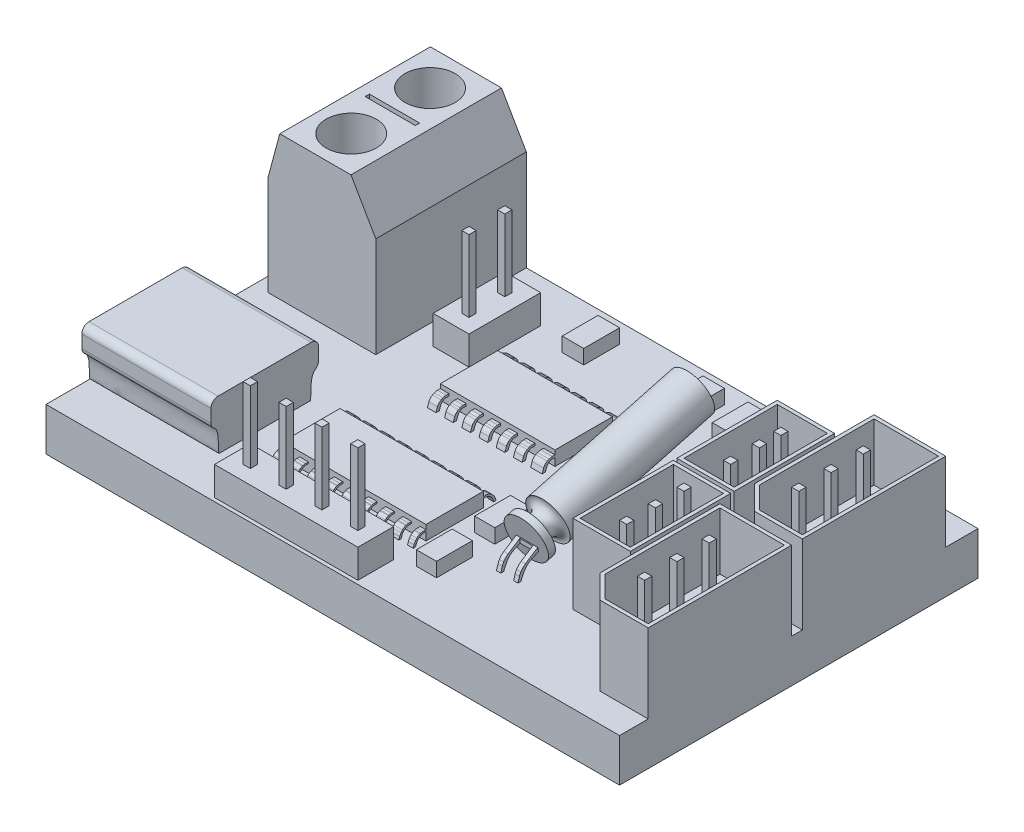
SolidWorks part; units mm, degrees
ref_plane "Front Plane" through (0, 0, 0) normal (0, 0, 1) x (1, 0, 0)
ref_plane "Top Plane" through (0, 0, 0) normal (0, 1, 0) x (1, 0, 0)
ref_plane "Right Plane" through (0, 0, 0) normal (1, 0, 0) x (0, 0, -1)
sketch "Sketch2" plane through (0, 0, 0) normal (0, 1, 0) x (1, 0, 0)
  line L1 (20, -12.5) -> (-20, -12.5)
  line L2 (20, -12.5) -> (20, 12.5)
  line L3 (20, 12.5) -> (-20, 12.5)
  line L4 (-20, -12.5) -> (-20, 12.5)
  line L5 (20, -12.5) -> (-20, 12.5) construction
  line L6 (20, 12.5) -> (-20, -12.5) construction
  point P0 (0, 0)
  dimension "D1" = 40
  dimension "D2" = 25
extrude "Boss-Extrude1" add sketch "Sketch2" against normal blind 3
sketch "Sketch3" plane through (0, 0, 0) normal (0, 1, 0) x (1, 0, 0)
  line L0 (20, 12.5) -> (-20, 12.5) construction
  line L1 (-19, 12.5) -> (-11.5, 12.5)
  line L2 (-19, 12.5) -> (-19, 2)
  line L3 (-19, 2) -> (-11.5, 2)
  line L4 (-11.5, 12.5) -> (-11.5, 2)
  line L5 (-20, 12.5) -> (-20, -12.5) construction
  dimension "D1" = 7.5
  dimension "D2" = 10.5
  dimension "D3" = 1
extrude "Boss-Extrude2" add sketch "Sketch3" along normal blind 10
sketch "Sketch4" plane through (0, 0, -2) normal (0, 0, 1) x (1, 0, 0)
  line L0 (-19, 7) -> (-18.1962, 10)
  line L1 (-19, 10) -> (-19, 0) construction
  line L2 (-19, 10) -> (-11.5, 10) construction
  line L3 (-18.1962, 10) -> (-19, 10)
  line L4 (-19, 10) -> (-19, 7)
  line L5 (-11.5, 7) -> (-13.2321, 10)
  line L6 (-11.5, 10) -> (-11.5, 0) construction
  line L7 (-13.2321, 10) -> (-11.5, 10)
  line L8 (-11.5, 10) -> (-11.5, 7)
  dimension "D1" = 3
  dimension "D2" = 3
  dimension "D3" = 15
  dimension "D4" = 30
extrude "Cut-Extrude1" cut sketch "Sketch4" against normal up to surface (10.5 mm away) up to face at (-7.625, 1.75, -12.5)
sketch "Sketch5" plane through (0, 10, 0) normal (0, 1, 0) x (1, 0, 0)
  line L0 (-13.2321, 12.5) -> (-18.1962, 12.5) construction
  line L1 (-17.4641, 7.522) -> (-13.9641, 7.522)
  line L2 (-17.4641, 7.522) -> (-17.4641, 7.222)
  line L3 (-17.4641, 7.222) -> (-13.9641, 7.222)
  line L4 (-13.9641, 7.522) -> (-13.9641, 7.222)
  line L5 (-19, 2) -> (-11.5, 2) construction
  circle A0 centre (-15.7141, 10) radius 1.75
  circle A1 centre (-15.7141, 4.5) radius 1.75
  point P10 (-15.7141, 12.5)
  point P11 (-15.7141, 7.522)
  dimension "D3" = 3.5
  dimension "D4" = 3.5
  dimension "D1" = 0.3
  dimension "D2" = 3.5
  dimension "D5" = 2.5
  dimension "D6" = 2.5
extrude "Cut-Extrude2" cut sketch "Sketch5" against normal blind 5
sketch "Sketch6" plane through (-19, 0, 0) normal (-1, 0, 0) x (0, 0, 1)
  line L0 (-2, 7) -> (-2, 0) construction
  line L1 (-12, 5.5) -> (-7.5, 5.5)
  line L2 (-12, 5.5) -> (-12, 1)
  line L3 (-12, 1) -> (-7.5, 1)
  line L4 (-7.5, 5.5) -> (-7.5, 1)
  line L5 (-12, 5.5) -> (-7.5, 1) construction
  line L6 (-12, 1) -> (-7.5, 5.5) construction
  line L7 (-7, 5.5) -> (-2.5, 5.5)
  line L8 (-7, 5.5) -> (-7, 1)
  line L9 (-7, 1) -> (-2.5, 1)
  line L10 (-2.5, 5.5) -> (-2.5, 1)
  line L11 (-7, 5.5) -> (-2.5, 1) construction
  line L12 (-7, 1) -> (-2.5, 5.5) construction
  line L13 (-12.5, 7) -> (-12.5, 0) construction
  line L14 (-12.5, 0) -> (-2, 0) construction
  point P0 (-9.75, 3.25)
  point P5 (-4.75, 3.25)
  dimension "D1" = 4.5
  dimension "D2" = 4.5
  dimension "D3" = 4.5
  dimension "D4" = 4.5
  dimension "D5" = 0.5
  dimension "D6" = 0.5
  dimension "D7" = 1
extrude "Cut-Extrude3" cut sketch "Sketch6" against normal blind 5
sketch "Sketch7" plane through (0, 0, 0) normal (0, 1, 0) x (1, 0, 0)
  line L0 (-20, 12.5) -> (-20, -12.5) construction
  line L1 (-11, -10) -> (-20, -10)
  line L2 (-11, -10) -> (-11, -2.5)
  line L3 (-11, -2.5) -> (-20, -2.5)
  line L4 (-20, -10) -> (-20, -2.5)
  line L5 (-11, -10) -> (-20, -2.5) construction
  line L6 (-11, -2.5) -> (-20, -10) construction
  line L7 (-20, -12.5) -> (20, -12.5) construction
  point P0 (-15.5, -6.25)
  dimension "D1" = 7.5
  dimension "D2" = 9
  dimension "D3" = 2.5
extrude "Boss-Extrude3" add sketch "Sketch7" along normal blind 3.5
sketch "Sketch8" plane through (-20, 0, 0) normal (-1, 0, 0) x (0, 0, 1)
  line L0 (6.25, 5.2143) -> (6.25, -0.441) construction
  line L1 (2.5, 3.5) -> (10, 3.5) construction
  line L2 (2.5, 3.5) -> (2.5, 0) construction
  line L3 (2.5, 0) -> (3.1127, 0)
  line L4 (2.5, 1.75) -> (2.5, 0)
  line L5 (10, 1.75) -> (10, 0)
  line L6 (10, 0) -> (9.3873, 0)
  spline S0 degree 3 poles (2.5, 1.75) (3.2855, 1.8357) (2.8866, -0.1418) (3.1127, 0) knots 0 0 0 0 1 1 1 1
  spline S1 degree 3 poles (10, 1.75) (9.2145, 1.8357) (9.6134, -0.1418) (9.3873, 0) knots 0 0 0 0 1 1 1 1
  point P4 (6.25, 3.5)
  line M15 (10, 0) -> (10, 3.5)
  line M17 (2.5, 3.5) -> (2.5, 0)
extrude "Cut-Extrude4" cut sketch "Sketch8" against normal blind 13.5 contours S0 L3 M17 | S1 L6 M15 region at (-20, 0.8013, 2.7456) region at (-20, 0.8013, 9.7544)
fillet "Fillet1" radius 0.5 4 edges at (-15.5, 1.75, 10) (-15.5, 1.75, 2.5) (-15.5, 3.5, 2.5) (-15.5, 3.5, 10)
sketch "Sketch9" plane through (-20, 0, 0) normal (-1, 0, 0) x (0, 0, 1)
  line L0 (3.25, 0.25) -> (9.25, 0.25)
  line L1 (6.25, 3.8986) -> (6.25, 0.8013) construction
  line L2 (3, 3.5) -> (9.5, 3.5) construction
  line L3 (9.4263, 0) -> (12.5, 0) construction
  line L4 (9.4639, 3.25) -> (3.0361, 3.25)
  spline S0 degree 3 poles (9.25, 0.25) (9.2002, 0.8034) (9.2979, 1.1822) (9.4331, 1.8514) (9.7825, 1.9035) (9.8466, 2.3039) (9.7756, 2.7644) (9.8573, 3.2635) (9.4639, 3.25) knots 0 0 0 0 0.398944 0.460389 0.554943 0.650182 0.770421 1 1 1 1
  spline S1 degree 3 poles (3.25, 0.25) (3.2998, 0.8034) (3.2021, 1.1822) (3.0669, 1.8514) (2.7175, 1.9035) (2.6534, 2.3039) (2.7244, 2.7644) (2.6427, 3.2635) (3.0361, 3.25) knots 0 0 0 0 0.398944 0.460389 0.554943 0.650182 0.770421 1 1 1 1
  point P6 (6.25, 3.5)
  point P14 (6.25, 0.25)
  point P27 (6.25, 3.25)
  dimension "D1" = 3
  dimension "D2" = 0.25
  dimension "D3" = 0.25
extrude "Cut-Extrude5" cut sketch "Sketch9" against normal blind 8.5
sketch "Sketch10" plane through (0, 0, 0) normal (0, 1, 0) x (1, 0, 0)
  line L0 (-11.5, 2) -> (-11.5, 12.5) construction
  line L1 (-10, 9.5) -> (-7.5, 9.5)
  line L2 (-10, 9.5) -> (-10, 4.5)
  line L3 (-10, 4.5) -> (-7.5, 4.5)
  line L4 (-7.5, 9.5) -> (-7.5, 4.5)
  line L5 (-10, 9.5) -> (-7.5, 4.5) construction
  line L6 (-10, 4.5) -> (-7.5, 9.5) construction
  line L7 (20, 12.5) -> (-11.5, 12.5) construction
  point P0 (-8.75, 7)
  dimension "D1" = 5
  dimension "D2" = 2.5
  dimension "D3" = 1.5
  dimension "D4" = 3
extrude "Boss-Extrude4" add sketch "Sketch10" along normal blind 2
sketch "Sketch11" plane through (0, 2, 0) normal (0, 1, 0) x (1, 0, 0)
  line L0 (-7.5, 9.5) -> (-10, 9.5) construction
  line L1 (-8.5, 8) -> (-9, 8)
  line L2 (-8.5, 8) -> (-8.5, 8.5)
  line L3 (-8.5, 8.5) -> (-9, 8.5)
  line L4 (-9, 8) -> (-9, 8.5)
  line L5 (-8.5, 8) -> (-9, 8.5) construction
  line L6 (-8.5, 8.5) -> (-9, 8) construction
  line L7 (-8.5027, 5.5) -> (-9.0027, 5.5)
  line L8 (-8.5027, 5.5) -> (-8.5027, 6)
  line L9 (-8.5027, 6) -> (-9.0027, 6)
  line L10 (-9.0027, 5.5) -> (-9.0027, 6)
  line L11 (-8.5027, 5.5) -> (-9.0027, 6) construction
  line L12 (-8.5027, 6) -> (-9.0027, 5.5) construction
  line L13 (-7.5, 4.5) -> (-7.5, 9.5) construction
  line L14 (-10, 4.5) -> (-7.5, 4.5) construction
  point P0 (-8.75, 8.25)
  point P5 (-8.7527, 5.75)
  dimension "D1" = 0.5
  dimension "D2" = 0.5
  dimension "D3" = 0.5
  dimension "D4" = 0.5
  dimension "D5" = 1.25
  dimension "D6" = 1.25
  dimension "D7" = 1.2527
  dimension "D8" = 1.25
extrude "Boss-Extrude5" add sketch "Sketch11" along normal blind 5
sketch "Sketch12" plane through (0, 0, 0) normal (0, 1, 0) x (1, 0, 0)
  line L0 (-11, -9.5) -> (-11, -3) construction
  line L1 (-8.5, -9.75) -> (1.5, -9.75)
  line L2 (-8.5, -9.75) -> (-8.5, -12.25)
  line L3 (-8.5, -12.25) -> (1.5, -12.25)
  line L4 (1.5, -9.75) -> (1.5, -12.25)
  line L5 (-20, -12.5) -> (20, -12.5) construction
  dimension "D1" = 2.5
  dimension "D2" = 10
  dimension "D3" = 2.5
  dimension "D4" = 0.25
extrude "Boss-Extrude6" add sketch "Sketch12" along normal blind 2
sketch "Sketch13" plane through (0, 2, 0) normal (0, 1, 0) x (1, 0, 0)
  line L0 (-8.5, -9.75) -> (-8.5, -12.25) construction
  line L1 (-7, -11.25) -> (-7.5, -11.25)
  line L2 (-7, -11.25) -> (-7, -10.75)
  line L3 (-7, -10.75) -> (-7.5, -10.75)
  line L4 (-7.5, -11.25) -> (-7.5, -10.75)
  line L5 (-7, -11.25) -> (-7.5, -10.75) construction
  line L6 (-7, -10.75) -> (-7.5, -11.25) construction
  line L8 (1.5, -9.75) -> (-8.5, -9.75) construction
  line L9 (-5, -11.25) -> (-5, -10.75)
  line L10 (-4.5, -10.75) -> (-5, -10.75)
  line L11 (-4.5, -11.25) -> (-4.5, -10.75)
  line L12 (-4.5, -11.25) -> (-5, -11.25)
  line L13 (-2.5, -11.25) -> (-2.5, -10.75)
  line L14 (-2, -10.75) -> (-2.5, -10.75)
  line L15 (-2, -11.25) -> (-2, -10.75)
  line L16 (-2, -11.25) -> (-2.5, -11.25)
  line L17 (0, -11.25) -> (0, -10.75)
  line L18 (0.5, -10.75) -> (0, -10.75)
  line L19 (0.5, -11.25) -> (0.5, -10.75)
  line L20 (0.5, -11.25) -> (0, -11.25)
  point P0 (-7.25, -11)
  dimension "D1" = 1.25
  dimension "D2" = 1.25
  dimension "D3" = 0.5
  dimension "D4" = 0.5
  dimension "D5" = 4
extrude "Boss-Extrude7" add sketch "Sketch13" along normal blind 5
sketch "Sketch14" plane through (0, 0, 0) normal (0, 1, 0) x (1, 0, 0)
  line L0 (-7.5, 4.5) -> (-7.5, 9.5) construction
  line L1 (-6.5, 5.5) -> (1.5, 5.5)
  line L2 (-6.5, 5.5) -> (-6.5, 1.5)
  line L3 (-6.5, 1.5) -> (1.5, 1.5)
  line L4 (1.5, 5.5) -> (1.5, 1.5)
  line L5 (-8.5, -3.5) -> (1.5, -3.5)
  line L6 (-8.5, -3.5) -> (-8.5, -7.5)
  line L7 (-8.5, -7.5) -> (1.5, -7.5)
  line L8 (1.5, -3.5) -> (1.5, -7.5)
  line L9 (20, 12.5) -> (-11.5, 12.5) construction
  dimension "D1" = 8
  dimension "D2" = 4
  dimension "D3" = 4
  dimension "D4" = 10
  dimension "D5" = 1
  dimension "D6" = 7
  dimension "D7" = 5
extrude "Boss-Extrude8" add sketch "Sketch14" along normal blind 1
sketch "Sketch15" plane through (1.5, 0, 0) normal (1, 0, 0) x (0, 0, -1)
  line L0 (1.5, 0.7025) -> (1.3027, 0.7025)
  line L1 (1.5, 1) -> (1.5, 0) construction
  line L2 (1.0838, 0.6521) -> (0.9577, 0.5907)
  line L3 (0.704, 0.3042) -> (0.599, 0)
  line L4 (-12.5, 0) -> (12.5, 0) construction
  line L5 (0.599, 0) -> (0.8295, 0)
  line L6 (0.8295, 0) -> (0.9119, 0.2391)
  line L7 (1.1657, 0.5256) -> (1.216, 0.5501)
  line L8 (1.216, 0.5501) -> (1.5, 0.5501)
  line L9 (3.5, 2.4985) -> (3.5, 0.0788) construction
  line L10 (1.5, 1) -> (5.5, 1) construction
  line L11 (1.5, 0.7025) -> (1.5, 0.5501)
  line L12 (5.5, 0.7025) -> (5.5, 0.5501)
  line L13 (5.784, 0.5501) -> (5.5, 0.5501)
  line L14 (5.8343, 0.5256) -> (5.784, 0.5501)
  line L15 (6.1705, 0) -> (6.0881, 0.2391)
  line L16 (6.401, 0) -> (6.1705, 0)
  line L17 (6.296, 0.3042) -> (6.401, 0)
  line L18 (5.9162, 0.6521) -> (6.0423, 0.5907)
  line L19 (5.5, 0.7025) -> (5.6973, 0.7025)
  arc A0 (1.3027, 0.7025) -> (1.0838, 0.6521) centre (1.3027, 0.2025) ccw
  arc A1 (0.9119, 0.2391) -> (1.1657, 0.5256) centre (1.3846, 0.076) cw
  arc A2 (0.704, 0.3042) -> (0.9577, 0.5907) centre (1.1767, 0.1412) cw
  arc A3 (6.296, 0.3042) -> (6.0423, 0.5907) centre (5.8233, 0.1412) ccw
  arc A4 (6.0881, 0.2391) -> (5.8343, 0.5256) centre (5.6154, 0.076) ccw
  arc A5 (5.6973, 0.7025) -> (5.9162, 0.6521) centre (5.6973, 0.2025) cw
  point P16 (3.5, 1)
  dimension "D1" = 0.5
extrude "Boss-Extrude9" add sketch "Sketch15" against normal up to surface (8 mm away) up to face at (-6.5, 0.5, -3.5)
sketch "Sketch16" plane through (1.5, 0, 0) normal (1, 0, 0) x (0, 0, -1)
  line L0 (-7.5, 0.6782) -> (-7.7045, 0.6782)
  line L1 (-7.5, 1) -> (-7.5, 0) construction
  line L2 (-7.8691, 0.6503) -> (-7.9154, 0.6342)
  line L3 (-8.1339, 0.4833) -> (-8.2332, 0.3648)
  line L4 (-8.3282, 0.1901) -> (-8.3864, 0)
  line L5 (-12.5, 0) -> (12.5, 0) construction
  line L6 (-8.3864, 0) -> (-8.2252, 0)
  line L7 (-8.2252, 0) -> (-8.1768, 0.1579)
  line L8 (-8.0819, 0.3327) -> (-8.0568, 0.3626)
  line L9 (-7.9199, 0.4766) -> (-7.8668, 0.5066)
  line L10 (-7.6206, 0.5714) -> (-7.5, 0.5714)
  line L11 (-7.5, 0.6782) -> (-7.5, 0.5714)
  line L12 (-5.5, 2.2485) -> (-5.5, -1.2373) construction
  line L13 (-7.5, 1) -> (-3.5, 1) construction
  line L14 (-3.5, 0.6782) -> (-3.5, 0.5714)
  line L15 (-3.3794, 0.5714) -> (-3.5, 0.5714)
  line L16 (-3.0801, 0.4766) -> (-3.1332, 0.5066)
  line L17 (-2.9181, 0.3327) -> (-2.9432, 0.3626)
  line L18 (-2.7748, 0) -> (-2.8232, 0.1579)
  line L19 (-2.6136, 0) -> (-2.7748, 0)
  line L20 (-2.6718, 0.1901) -> (-2.6136, 0)
  line L21 (-2.8661, 0.4833) -> (-2.7668, 0.3648)
  line L22 (-3.1309, 0.6503) -> (-3.0846, 0.6342)
  line L23 (-3.5, 0.6782) -> (-3.2955, 0.6782)
  arc A1 (-7.7045, 0.6782) -> (-7.8691, 0.6503) centre (-7.7045, 0.1782) ccw
  arc A2 (-7.8668, 0.5066) -> (-7.6206, 0.5714) centre (-7.6206, 0.0714) cw
  arc A3 (-8.0568, 0.3626) -> (-7.9199, 0.4766) centre (-7.6737, 0.0414) cw
  arc A4 (-8.1768, 0.1579) -> (-8.0819, 0.3327) centre (-7.6987, 0.0115) cw
  arc A5 (-8.2332, 0.3648) -> (-8.3282, 0.1901) centre (-7.8501, 0.0436) ccw
  arc A6 (-7.9154, 0.6342) -> (-8.1339, 0.4833) centre (-7.7508, 0.1621) ccw
  arc A7 (-3.0846, 0.6342) -> (-2.8661, 0.4833) centre (-3.2492, 0.1621) cw
  arc A8 (-2.7668, 0.3648) -> (-2.6718, 0.1901) centre (-3.1499, 0.0436) cw
  arc A9 (-2.8232, 0.1579) -> (-2.9181, 0.3327) centre (-3.3013, 0.0115) ccw
  arc A10 (-2.9432, 0.3626) -> (-3.0801, 0.4766) centre (-3.3263, 0.0414) ccw
  arc A11 (-3.1332, 0.5066) -> (-3.3794, 0.5714) centre (-3.3794, 0.0714) ccw
  arc A12 (-3.2955, 0.6782) -> (-3.1309, 0.6503) centre (-3.2955, 0.1782) cw
  point P16 (-5.5, 1)
  dimension "D1" = 0.5
extrude "Boss-Extrude10" add sketch "Sketch16" against normal up to surface (10 mm away) up to face at (-8.5, 0.5, 5.5)
sketch "Sketch17" plane through (0, 0, 0) normal (0, 1, 0) x (1, 0, 0)
  line L0 (-6.5, 6.401) -> (1.5, 6.401) construction
  line L1 (-5.9, 6.401) -> (-5.3, 6.401)
  line L2 (-5.9, 6.401) -> (-5.9, 5.5)
  line L3 (-5.9, 5.5) -> (-5.3, 5.5)
  line L4 (-5.3, 6.401) -> (-5.3, 5.5)
  line L5 (-6.5, 5.5) -> (1.5, 5.5) construction
  line L6 (-6.5, 1.5) -> (1.5, 1.5) construction
  line L7 (-5.9, 1.5) -> (-5.3, 1.5)
  line L8 (-5.9, 1.5) -> (-5.9, 0.599)
  line L9 (-5.9, 0.599) -> (-5.3, 0.599)
  line L10 (-5.3, 1.5) -> (-5.3, 0.599)
  line L11 (-6.5, 0.599) -> (1.5, 0.599) construction
  line L12 (-6.5, 6.296) -> (-6.5, 6.0423) construction
  line L13 (-4.1, 1.5) -> (-4.1, 0.599)
  line L14 (-4.7, 1.5) -> (-4.1, 1.5)
  line L15 (-4.7, 1.5) -> (-4.7, 0.599)
  line L16 (-4.7, 0.599) -> (-4.1, 0.599)
  line L17 (-4.7, 5.5) -> (-4.1, 5.5)
  line L18 (-4.7, 6.401) -> (-4.7, 5.5)
  line L19 (-4.1, 6.401) -> (-4.1, 5.5)
  line L20 (-4.7, 6.401) -> (-4.1, 6.401)
  line L21 (-2.9, 1.5) -> (-2.9, 0.599)
  line L22 (-3.5, 1.5) -> (-2.9, 1.5)
  line L23 (-3.5, 1.5) -> (-3.5, 0.599)
  line L24 (-3.5, 0.599) -> (-2.9, 0.599)
  line L25 (-3.5, 5.5) -> (-2.9, 5.5)
  line L26 (-3.5, 6.401) -> (-3.5, 5.5)
  line L27 (-2.9, 6.401) -> (-2.9, 5.5)
  line L28 (-3.5, 6.401) -> (-2.9, 6.401)
  line L29 (-1.7, 1.5) -> (-1.7, 0.599)
  line L30 (-2.3, 1.5) -> (-1.7, 1.5)
  line L31 (-2.3, 1.5) -> (-2.3, 0.599)
  line L32 (-2.3, 0.599) -> (-1.7, 0.599)
  line L33 (-2.3, 5.5) -> (-1.7, 5.5)
  line L34 (-2.3, 6.401) -> (-2.3, 5.5)
  line L35 (-1.7, 6.401) -> (-1.7, 5.5)
  line L36 (-2.3, 6.401) -> (-1.7, 6.401)
  line L37 (-0.5, 1.5) -> (-0.5, 0.599)
  line L38 (-1.1, 1.5) -> (-0.5, 1.5)
  line L39 (-1.1, 1.5) -> (-1.1, 0.599)
  line L40 (-1.1, 0.599) -> (-0.5, 0.599)
  line L41 (-1.1, 5.5) -> (-0.5, 5.5)
  line L42 (-1.1, 6.401) -> (-1.1, 5.5)
  line L43 (-0.5, 6.401) -> (-0.5, 5.5)
  line L44 (-1.1, 6.401) -> (-0.5, 6.401)
  line L45 (0.7, 1.5) -> (0.7, 0.599)
  line L46 (0.1, 1.5) -> (0.7, 1.5)
  line L47 (0.1, 1.5) -> (0.1, 0.599)
  line L48 (0.1, 0.599) -> (0.7, 0.599)
  line L49 (0.1, 5.5) -> (0.7, 5.5)
  line L50 (0.1, 6.401) -> (0.1, 5.5)
  line L51 (0.7, 6.401) -> (0.7, 5.5)
  line L52 (0.1, 6.401) -> (0.7, 6.401)
  line L53 (-8.5, -2.6136) -> (1.5, -2.6136) construction
  line L54 (-7.9, -2.6136) -> (-7.3, -2.6136)
  line L55 (-7.9, -2.6136) -> (-7.9, -3.5)
  line L56 (-7.9, -3.5) -> (-7.3, -3.5)
  line L57 (-7.3, -2.6136) -> (-7.3, -3.5)
  line L58 (1.5, -3.5) -> (-8.5, -3.5) construction
  line L59 (-8.5, -7.5) -> (1.5, -7.5) construction
  line L60 (-7.9, -7.5) -> (-7.3, -7.5)
  line L61 (-7.9, -7.5) -> (-7.9, -8.3864)
  line L62 (-7.9, -8.3864) -> (-7.3, -8.3864)
  line L63 (-7.3, -7.5) -> (-7.3, -8.3864)
  line L64 (-8.5, -8.3864) -> (1.5, -8.3864) construction
  line L65 (-8.5, -2.8661) -> (-8.5, -3.0846) construction
  line L66 (-8.5, -7.7045) -> (-8.5, -7.8691) construction
  line L67 (-6.7, -2.6136) -> (-6.7, -3.5)
  line L68 (-6.7, -2.6136) -> (-6.1, -2.6136)
  line L69 (-6.1, -2.6136) -> (-6.1, -3.5)
  line L70 (-6.7, -3.5) -> (-6.1, -3.5)
  line L71 (-6.7, -7.5) -> (-6.7, -8.3864)
  line L72 (-6.7, -7.5) -> (-6.1, -7.5)
  line L73 (-6.1, -7.5) -> (-6.1, -8.3864)
  line L74 (-6.7, -8.3864) -> (-6.1, -8.3864)
  line L75 (-5.5, -2.6136) -> (-5.5, -3.5)
  line L76 (-5.5, -2.6136) -> (-4.9, -2.6136)
  line L77 (-4.9, -2.6136) -> (-4.9, -3.5)
  line L78 (-5.5, -3.5) -> (-4.9, -3.5)
  line L79 (-5.5, -7.5) -> (-5.5, -8.3864)
  line L80 (-5.5, -7.5) -> (-4.9, -7.5)
  line L81 (-4.9, -7.5) -> (-4.9, -8.3864)
  line L82 (-5.5, -8.3864) -> (-4.9, -8.3864)
  line L83 (-4.3, -2.6136) -> (-4.3, -3.5)
  line L84 (-4.3, -2.6136) -> (-3.7, -2.6136)
  line L85 (-3.7, -2.6136) -> (-3.7, -3.5)
  line L86 (-4.3, -3.5) -> (-3.7, -3.5)
  line L87 (-4.3, -7.5) -> (-4.3, -8.3864)
  line L88 (-4.3, -7.5) -> (-3.7, -7.5)
  line L89 (-3.7, -7.5) -> (-3.7, -8.3864)
  line L90 (-4.3, -8.3864) -> (-3.7, -8.3864)
  line L91 (-3.1, -2.6136) -> (-3.1, -3.5)
  line L92 (-3.1, -2.6136) -> (-2.5, -2.6136)
  line L93 (-2.5, -2.6136) -> (-2.5, -3.5)
  line L94 (-3.1, -3.5) -> (-2.5, -3.5)
  line L95 (-3.1, -7.5) -> (-3.1, -8.3864)
  line L96 (-3.1, -7.5) -> (-2.5, -7.5)
  line L97 (-2.5, -7.5) -> (-2.5, -8.3864)
  line L98 (-3.1, -8.3864) -> (-2.5, -8.3864)
  line L99 (-1.9, -2.6136) -> (-1.9, -3.5)
  line L100 (-1.9, -2.6136) -> (-1.3, -2.6136)
  line L101 (-1.3, -2.6136) -> (-1.3, -3.5)
  line L102 (-1.9, -3.5) -> (-1.3, -3.5)
  line L103 (-1.9, -7.5) -> (-1.9, -8.3864)
  line L104 (-1.9, -7.5) -> (-1.3, -7.5)
  line L105 (-1.3, -7.5) -> (-1.3, -8.3864)
  line L106 (-1.9, -8.3864) -> (-1.3, -8.3864)
  line L107 (-0.7, -2.6136) -> (-0.7, -3.5)
  line L108 (-0.7, -2.6136) -> (-0.1, -2.6136)
  line L109 (-0.1, -2.6136) -> (-0.1, -3.5)
  line L110 (-0.7, -3.5) -> (-0.1, -3.5)
  line L111 (-0.7, -7.5) -> (-0.7, -8.3864)
  line L112 (-0.7, -7.5) -> (-0.1, -7.5)
  line L113 (-0.1, -7.5) -> (-0.1, -8.3864)
  line L114 (-0.7, -8.3864) -> (-0.1, -8.3864)
  line L115 (0.5, -2.6136) -> (0.5, -3.5)
  line L116 (0.5, -2.6136) -> (1.1, -2.6136)
  line L117 (1.1, -2.6136) -> (1.1, -3.5)
  line L118 (0.5, -3.5) -> (1.1, -3.5)
  line L119 (0.5, -7.5) -> (0.5, -8.3864)
  line L120 (0.5, -7.5) -> (1.1, -7.5)
  line L121 (1.1, -7.5) -> (1.1, -8.3864)
  line L122 (0.5, -8.3864) -> (1.1, -8.3864)
  dimension "D1" = 0.6
  dimension "D2" = 0.6
  dimension "D3" = 0.6
  dimension "D5" = 0.6
  dimension "D6" = 0.6
  dimension "D7" = 0.6
  dimension "D8" = 0.6
  dimension "D4" = 6
  dimension "D9" = 8
extrude "Cut-Extrude6" cut sketch "Sketch17" along normal blind 1
sketch "Sketch18" plane through (0, 0, 0) normal (0, 1, 0) x (1, 0, 0)
  line L0 (15.25, 10) -> (19.75, 10)
  line L1 (19.75, 10) -> (19.75, 0.5)
  line L2 (19.75, 0.5) -> (16.75, 0.5)
  line L5 (16.75, 0.5) -> (15.25, 2)
  line L6 (15.25, 2) -> (15.25, 10)
  line L7 (20, -12.5) -> (20, 12.5) construction
  line L8 (20, 12.5) -> (-11.5, 12.5) construction
  line L9 (15.25, -0.75) -> (19.75, -0.75)
  line L10 (19.75, -0.75) -> (19.75, -10.25)
  line L11 (19.75, -10.25) -> (16.75, -10.25)
  line L12 (16.75, -10.25) -> (15.25, -8.75)
  line L13 (15.25, -8.75) -> (15.25, -0.75)
  line L14 (-20, -12.5) -> (20, -12.5) construction
  line L21 (11, 7.5) -> (14.5, 7.5)
  line L22 (11, 7.5) -> (11, 1)
  line L23 (11, 1) -> (14.5, 1)
  line L24 (14.5, 7.5) -> (14.5, 1)
  line L25 (11, 0.25) -> (14.5, 0.25)
  line L26 (11, 0.25) -> (11, -6.25)
  line L27 (11, -6.25) -> (14.5, -6.25)
  line L28 (14.5, 0.25) -> (14.5, -6.25)
  dimension "D1" = 9.5
  dimension "D2" = 4.5
  dimension "D3" = 135
  dimension "D4" = 0.25
  dimension "D5" = 2.5
  dimension "D6" = 3
  dimension "D7" = 135
  dimension "D8" = 3
  dimension "D9" = 9.5
  dimension "D10" = 4.5
  dimension "D11" = 0.25
  dimension "D12" = 2.25
  dimension "D13" = 3.5
  dimension "D14" = 3.5
  dimension "D15" = 6.5
  dimension "D16" = 6.5
  dimension "D17" = 0.75
  dimension "D18" = 0.75
  dimension "D19" = 2.5
  dimension "D20" = 0.75
extrude "Extrude-Thin1" add sketch "Sketch18" along normal blind 5.5 thin thin type one direction wall 0.25
sketch "Sketch19" plane through (0, 0, 0) normal (0, 1, 0) x (1, 0, 0)
  line L0 (19.75, 0.5) -> (19.75, 10) construction
  line L1 (11, 7.5) -> (14.5, 7.5)
  line L2 (11, 7.5) -> (11, 1)
  line L3 (11, 1) -> (14.5, 1)
  line L4 (14.5, 7.5) -> (14.5, 1)
  line L5 (11, 0.25) -> (14.5, 0.25)
  line L6 (11, 0.25) -> (11, -6.25)
  line L7 (11, -6.25) -> (14.5, -6.25)
  line L8 (14.5, 0.25) -> (14.5, -6.25)
  line L9 (19.75, 10) -> (15.25, 10) construction
  line L10 (15.25, 10) -> (15.25, 2) construction
  line L11 (15.25, 2) -> (16.75, 0.5) construction
  line L12 (16.75, 0.5) -> (19.75, 0.5) construction
  line L13 (19.75, -10.25) -> (19.75, -0.75) construction
  line L14 (19.75, -0.75) -> (15.25, -0.75) construction
  line L15 (15.25, -0.75) -> (15.25, -8.75) construction
  line L16 (15.25, -8.75) -> (16.75, -10.25) construction
  line L17 (16.75, -10.25) -> (19.75, -10.25) construction
  line L18 (19.75, 0.5) -> (19.75, 10)
  line L19 (19.75, 10) -> (15.25, 10)
  line L20 (15.25, 10) -> (15.25, 2)
  line L21 (15.25, 2) -> (16.75, 0.5)
  line L22 (16.75, 0.5) -> (19.75, 0.5)
  line L23 (19.75, -10.25) -> (19.75, -0.75)
  line L24 (19.75, -0.75) -> (15.25, -0.75)
  line L25 (15.25, -0.75) -> (15.25, -8.75)
  line L26 (15.25, -8.75) -> (16.75, -10.25)
  line L27 (16.75, -10.25) -> (19.75, -10.25)
extrude "Boss-Extrude11" add sketch "Sketch19" along normal blind 1.5
sketch "Sketch20" plane through (0, 1.5, 0) normal (0, 1, 0) x (1, 0, 0)
  line L0 (16.5, 5.25) -> (17, 5.25)
  line L1 (16.5, 8) -> (17, 8)
  line L2 (16.5, 8) -> (16.5, 7.5)
  line L3 (16.5, 7.5) -> (17, 7.5)
  line L4 (17, 8) -> (17, 7.5)
  line L5 (16.5, 5.25) -> (16.5, 5.75)
  line L6 (16.5, 5.75) -> (17, 5.75)
  line L7 (17, 5.25) -> (17, 5.75)
  line L8 (16.5, 3.5) -> (17, 3.5)
  line L9 (16.5, 3.5) -> (16.5, 3)
  line L10 (16.5, 3) -> (17, 3)
  line L11 (17, 3.5) -> (17, 3)
  line L12 (16.5, -2.75) -> (17, -2.75)
  line L13 (16.5, -2.75) -> (16.5, -3.25)
  line L14 (16.5, -3.25) -> (17, -3.25)
  line L15 (17, -2.75) -> (17, -3.25)
  line L16 (16.5, -5) -> (17, -5)
  line L17 (16.5, -5) -> (16.5, -5.5)
  line L18 (16.5, -5.5) -> (17, -5.5)
  line L19 (17, -5) -> (17, -5.5)
  line L20 (16.5, -7.25) -> (17, -7.25)
  line L21 (16.5, -7.25) -> (16.5, -7.75)
  line L22 (16.5, -7.75) -> (17, -7.75)
  line L23 (17, -7.25) -> (17, -7.75)
  line L24 (12.5, -0.5) -> (13, -0.5)
  line L25 (12.5, -0.5) -> (12.5, -1)
  line L26 (12.5, -1) -> (13, -1)
  line L27 (13, -0.5) -> (13, -1)
  line L28 (12.5, -2.5) -> (13, -2.5)
  line L29 (12.5, -2.5) -> (12.5, -3)
  line L30 (12.5, -3) -> (13, -3)
  line L31 (13, -2.5) -> (13, -3)
  line L32 (12.5, -4.5) -> (13, -4.5)
  line L33 (12.5, -4.5) -> (12.5, -5)
  line L34 (12.5, -5) -> (13, -5)
  line L35 (13, -4.5) -> (13, -5)
  line L36 (12.5, 2.75) -> (13, 2.75)
  line L37 (12.5, 2.75) -> (12.5, 2.25)
  line L38 (12.5, 2.25) -> (13, 2.25)
  line L39 (13, 2.75) -> (13, 2.25)
  line L40 (12.5, 4.75) -> (13, 4.75)
  line L41 (12.5, 4.75) -> (12.5, 4.25)
  line L42 (12.5, 4.25) -> (13, 4.25)
  line L43 (13, 4.75) -> (13, 4.25)
  line L44 (12.5, 5.75) -> (13, 5.75)
  line L45 (12.5, 5.75) -> (12.5, 6.25)
  line L46 (12.5, 6.25) -> (13, 6.25)
  line L47 (13, 5.75) -> (13, 6.25)
  line L48 (11, 1) -> (14.5, 1) construction
  line L49 (11, 7.5) -> (11, 1) construction
  line L51 (11, -6.25) -> (14.5, -6.25) construction
  line L52 (19.75, 10) -> (15.25, 10) construction
  line L53 (15.25, 10) -> (15.25, 2) construction
  line L55 (19.75, -0.75) -> (15.25, -0.75) construction
  dimension "D1" = 0.5
  dimension "D2" = 0.5
  dimension "D3" = 1.5
  dimension "D4" = 1.5
  dimension "D5" = 1.25
  dimension "D6" = 1.5
  dimension "D7" = 0.5
  dimension "D8" = 0.5
  dimension "D9" = 0.5
  dimension "D10" = 0.5
  dimension "D11" = 0.5
  dimension "D12" = 0.5
  dimension "D13" = 0.5
  dimension "D14" = 0.5
  dimension "D15" = 0.5
  dimension "D16" = 0.5
  dimension "D17" = 1.25
  dimension "D18" = 1.5
  dimension "D19" = 1.5
  dimension "D20" = 0.5
  dimension "D21" = 0.5
  dimension "D22" = 1.75
  dimension "D23" = 1.75
  dimension "D24" = 2
  dimension "D25" = 1.25
  dimension "D26" = 1.75
  dimension "D27" = 1.75
  dimension "D28" = 0.5
  dimension "D29" = 0.5
  dimension "D30" = 0.5
  dimension "D31" = 0.5
  dimension "D32" = 2
extrude "Boss-Extrude12" add sketch "Sketch20" along normal up to surface (4 mm away) up to face at (12.75, 5.5, -4.25)
ref_plane "Plane1" through (6.5, 0, 0) normal (1, 0, 0) x (0, 0, -1)
sketch "Sketch21" plane through (6.5, 0, 0) normal (1, 0, 0) x (0, 0, -1)
  line L0 (-8.8936, 0.7228) -> (16.1457, 7.4321) construction
  line L1 (-2.6456, 0) -> (5.105, 0) construction
  line L2 (-5.5, 1.6321) -> (-5.1118, 0.1832)
  line L3 (-3.6099, 0.5856) -> (6.4793, 3.289)
  line L4 (6.4793, 3.289) -> (6.0911, 4.7379)
  line L5 (-5.1118, 0.1832) -> (-4.6288, 0.3126)
  line L6 (-5.5, 1.6321) -> (6.0911, 4.7379)
  arc A0 (-3.6099, 0.5856) -> (-4.6288, 0.3126) centre (-4.1597, 0.5998) ccw
  dimension "D3" = 0.55
  dimension "D1" = 15
  dimension "D2" = 3
  dimension "D4" = 1.5
  dimension "D5" = 12
  dimension "D6" = 0.5
  dimension "D7" = 5.5
revolve "Revolve1" add sketch "Sketch21" angle 360 about L0
sketch "Sketch22" plane through (6.5, 0, 0) normal (1, 0, 0) x (0, 0, -1)
  line L0 (-0.2315, 0) -> (-9.1302, 0) construction
  line L1 (-5.3855, 1.2048) -> (-5.9749, 0.9066)
  line L2 (-5.8882, 3.081) -> (-5.1118, 0.1832) construction
  line L3 (-6.3822, 0.5266) -> (-6.4098, 0.4803)
  line L4 (-6.4684, 0.3662) -> (-6.6273, 0)
  line L5 (-6.6273, 0) -> (-6.8363, 0)
  line L6 (-6.8363, 0) -> (-6.7304, 0.3506)
  line L7 (-6.632, 0.5737) -> (-6.6309, 0.5755)
  line L8 (-6.3158, 0.9024) -> (-5.4541, 1.4608)
  line L9 (-5.4541, 1.4608) -> (-5.3855, 1.2048)
  arc A0 (-5.9749, 0.9066) -> (-6.3822, 0.5266) centre (-5.5234, 0.0143) ccw
  arc A1 (-6.4098, 0.4803) -> (-6.4684, 0.3662) centre (-5.551, -0.0319) ccw
  arc A2 (-6.7304, 0.3506) -> (-6.632, 0.5737) centre (-5.7732, 0.0614) cw
  arc A3 (-6.6309, 0.5755) -> (-6.3158, 0.9024) centre (-5.7721, 0.0632) cw
  dimension "D1" = 1
extrude "Boss-Extrude13" add sketch "Sketch22" along normal mid plane 1.5
sketch "Sketch24" plane through (0, 0, 12.5) normal (0, 0, 1) x (1, 0, 0)
  line L0 (7.25, 1.4608) -> (5.75, 1.4608) construction
  line L1 (6.05, 1.4608) -> (6.95, 1.4608)
  line L2 (6.05, 1.4608) -> (6.05, 0)
  line L3 (6.05, 0) -> (6.95, 0)
  line L4 (6.95, 1.4608) -> (6.95, 0)
  line L5 (-20, 0) -> (20, 0) construction
  line L6 (5.75, 1.4608) -> (5.75, 0.9024) construction
  line L7 (7.25, 1.4608) -> (7.25, 0.9024) construction
  dimension "D1" = 0.3
  dimension "D2" = 0.3
extrude "Cut-Extrude7" cut sketch "Sketch24" against normal blind 7
sketch "Sketch25" plane through (0, 0, 0) normal (0, 1, 0) x (1, 0, 0)
  line L0 (3.6854, 8.6309) -> (2.1854, 8.6309)
  line L1 (-3.6277, 8.6309) -> (-5.1277, 8.6309)
  line L2 (-3.6277, 8.6309) -> (-3.6277, 11.1309)
  line L3 (-3.6277, 11.1309) -> (-5.1277, 11.1309)
  line L4 (-5.1277, 8.6309) -> (-5.1277, 11.1309)
  line L5 (-3.6277, 8.6309) -> (-5.1277, 11.1309) construction
  line L6 (-3.6277, 11.1309) -> (-5.1277, 8.6309) construction
  line L7 (3.6854, 8.6309) -> (3.6854, 11.1309)
  line L8 (3.6854, 11.1309) -> (2.1854, 11.1309)
  line L9 (2.1854, 8.6309) -> (2.1854, 11.1309)
  line L10 (3.6854, 8.6309) -> (2.1854, 11.1309) construction
  line L11 (3.6854, 11.1309) -> (2.1854, 8.6309) construction
  line L12 (6.8331, 8.6309) -> (5.3331, 8.6309)
  line L13 (6.8331, 8.6309) -> (6.8331, 11.1309)
  line L14 (6.8331, 11.1309) -> (5.3331, 11.1309)
  line L15 (5.3331, 8.6309) -> (5.3331, 11.1309)
  line L16 (6.8331, 8.6309) -> (5.3331, 11.1309) construction
  line L17 (6.8331, 11.1309) -> (5.3331, 8.6309) construction
  line L18 (9.6668, 8.6309) -> (8.1668, 8.6309)
  line L19 (9.6668, 8.6309) -> (9.6668, 11.1309)
  line L20 (9.6668, 11.1309) -> (8.1668, 11.1309)
  line L21 (8.1668, 8.6309) -> (8.1668, 11.1309)
  line L22 (9.6668, 8.6309) -> (8.1668, 11.1309) construction
  line L23 (9.6668, 11.1309) -> (8.1668, 8.6309) construction
  line L24 (4.0958, -5.2967) -> (2.6919, -5.2967)
  line L25 (4.0958, -5.2967) -> (4.0958, -2.7967)
  line L26 (4.0958, -2.7967) -> (2.6919, -2.7967)
  line L27 (2.6919, -5.2967) -> (2.6919, -2.7967)
  line L28 (4.0958, -5.2967) -> (2.6919, -2.7967) construction
  line L29 (4.0958, -2.7967) -> (2.6919, -5.2967) construction
  line L30 (4.0958, -9.3613) -> (2.6919, -9.3613)
  line L31 (4.0958, -9.3613) -> (4.0958, -6.8613)
  line L32 (4.0958, -6.8613) -> (2.6919, -6.8613)
  line L33 (2.6919, -9.3613) -> (2.6919, -6.8613)
  line L34 (4.0958, -9.3613) -> (2.6919, -6.8613) construction
  line L35 (4.0958, -6.8613) -> (2.6919, -9.3613) construction
  point P0 (-4.3777, 9.8809)
  point P6 (2.9354, 9.8809)
  point P11 (6.0831, 9.8809)
  point P16 (8.9168, 9.8809)
  point P23 (3.3938, -4.0467)
  point P28 (3.3938, -8.1113)
  dimension "D1" = 1.5
  dimension "D2" = 2.5
  dimension "D3" = 2.5
  dimension "D4" = 2.5
  dimension "D5" = 2.5
  dimension "D6" = 2.5
  dimension "D7" = 2.5
extrude "Boss-Extrude14" add sketch "Sketch25" along normal blind 1
ref_plane "Plane2" through (0, -3, 0) normal (0, 1, 0) x (1, 0, 0)
sketch "Sketch26" plane through (0, -3, 0) normal (0, 1, 0) x (1, 0, 0)
  line L0 (-20, 12.5) -> (-20, -12.5) construction
  line L1 (20, 12.5) -> (-20, 12.5)
  line L2 (20, 12.5) -> (20, -12.5)
  line L3 (20, -12.5) -> (-20, -12.5)
  line L4 (-20, 12.5) -> (-20, -12.5)
  line L5 (20, 12.5) -> (-20, -12.5) construction
  line L6 (20, -12.5) -> (-20, 12.5) construction
  line L7 (-20, -9.4263) -> (-20, -12.5) construction
  point P0 (0, 0)
  dimension "D1" = 25
extrude "Boss-Extrude15" add sketch "Sketch26" along normal blind 3
